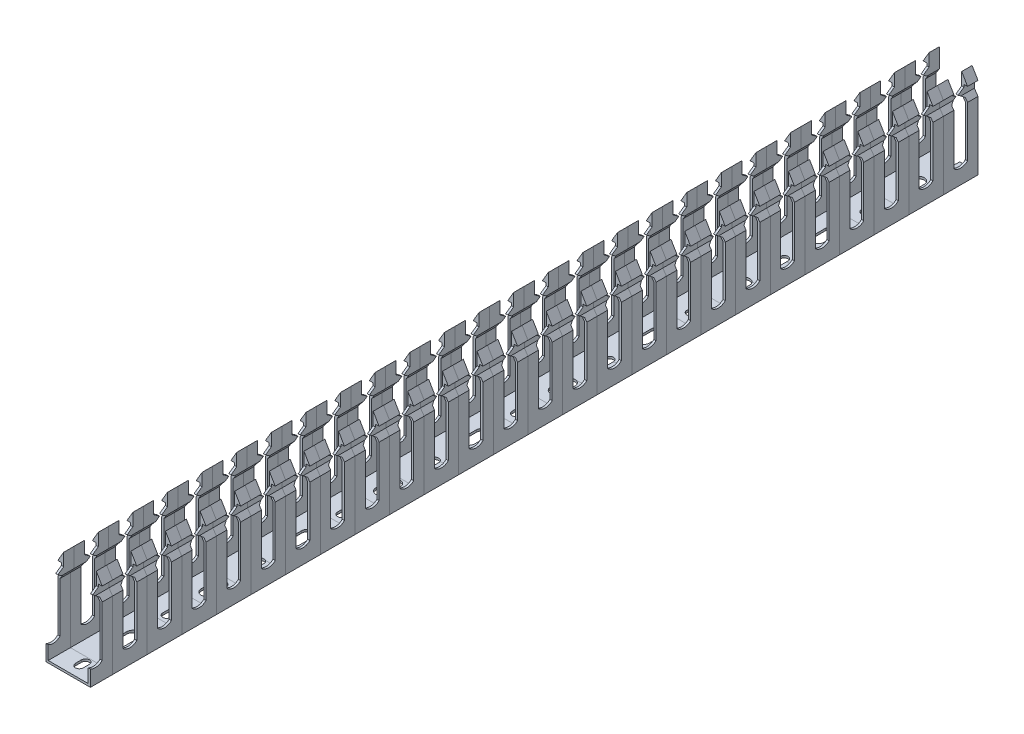
SolidWorks part; units mm, degrees
ref_plane "Front Plane" through (0, 0, 0) normal (0, 0, 1) x (1, 0, 0)
ref_plane "Top Plane" through (0, 0, 0) normal (0, 1, 0) x (1, 0, 0)
ref_plane "Right Plane" through (0, 0, 0) normal (1, 0, 0) x (0, 0, -1)
sketch "Sketch1" plane through (0, 0, 0) normal (0, 0, 1) x (1, 0, 0)
  line L1 (-12.7, -26.289) -> (12.7, -26.289)
  line L2 (-12.7, -26.289) -> (-12.7, 26.289)
  line L3 (-12.7, 26.289) -> (12.7, 26.289)
  line L4 (12.7, -26.289) -> (12.7, 26.289)
  line L5 (-12.7, -26.289) -> (12.7, 26.289) construction
  line L6 (-12.7, 26.289) -> (12.7, -26.289) construction
  point P0 (0, 0)
  dimension "D1" = 25.4
  dimension "D2" = 52.578
extrude "Boss-Extrude1" add sketch "Sketch1" along normal blind 19.812
sketch "Sketch2" plane through (12.7, 0, 0) normal (1, 0, 0) x (0, 0, -1)
  line L0 (-5.969, 26.289) -> (-5.969, 19.1453)
  line L1 (-19.812, 26.289) -> (0, 26.289) construction
  line L2 (-5.969, 19.1453) -> (-9.271, 16.764)
  line L3 (-9.271, 16.764) -> (-5.969, 14.3827)
  line L4 (-5.969, 14.3827) -> (-5.969, -16.3195)
  line L5 (-13.843, 26.289) -> (-13.843, 19.1453)
  line L6 (-13.843, 19.1453) -> (-10.541, 16.764)
  line L7 (-10.541, 16.764) -> (-13.843, 14.3827)
  line L8 (-13.843, 14.3827) -> (-13.843, -16.3195)
  line L9 (-13.843, 26.289) -> (-5.969, 26.289)
  line L10 (-13.843, -16.3195) -> (-5.969, -16.3195) construction
  line L11 (-10.541, 16.764) -> (-9.271, 16.764) construction
  line L12 (-13.843, 14.3827) -> (-5.969, 14.3827) construction
  line L13 (-13.843, 19.1453) -> (-5.969, 19.1453) construction
  line L14 (0, -26.289) -> (0, 26.289) construction
  line L15 (-13.843, 19.1453) -> (-13.843, 14.3827) construction
  line L16 (-5.969, 19.1453) -> (-5.969, 14.3827) construction
  line L17 (-19.812, -26.289) -> (0, -26.289) construction
  arc A0 (-5.969, -16.3195) -> (-13.843, -16.3195) centre (-9.906, -12.3825) cw
  dimension "D7" = 5.5678
  dimension "D1" = 7.874
  dimension "D2" = 1.27
  dimension "D3" = 9.525
  dimension "D4" = 7.1438
  dimension "D5" = 5.969
  dimension "D6" = 9.9695
extrude "Cut-Extrude2" cut sketch "Sketch2" against normal up to next
sketch "Sketch3" plane through (0, 0, 19.812) normal (0, 0, 1) x (1, 0, 0)
  line L0 (-11.43, 12.2331) -> (-11.43, -25.019)
  line L1 (-11.43, -25.019) -> (11.43, -25.019)
  line L2 (11.43, -25.019) -> (11.43, 12.2331)
  line L3 (11.43, 12.2331) -> (9.3339, 15.2441)
  line L4 (9.3339, 15.2441) -> (9.3339, 26.289)
  line L5 (12.7, 26.289) -> (-12.7, 26.289) construction
  line L6 (9.3339, 26.289) -> (12.7, 20.5631)
  line L7 (12.7, -26.289) -> (12.7, 26.289) construction
  line L8 (12.7, 20.5631) -> (10.6039, 20.5631)
  line L9 (10.6039, 20.5631) -> (10.6039, 15.6427)
  line L10 (-12.7, 26.289) -> (-12.7, -26.289) construction
  line L11 (10.6039, 15.6427) -> (13.6788, 11.2257)
  line L12 (-12.7, 20.5631) -> (-9.3339, 26.289)
  line L13 (-9.3339, 26.289) -> (-9.3339, 15.2441)
  line L14 (-9.3339, 15.2441) -> (-11.43, 12.2331)
  line L15 (-9.3339, 15.2441) -> (9.3339, 15.2441) construction
  line L16 (-12.7, 20.5631) -> (12.7, 20.5631) construction
  line L17 (13.6788, 11.2257) -> (13.6788, 29.8905)
  line L18 (13.6788, 29.8905) -> (-13.6788, 29.8905)
  line L19 (-13.6788, 29.8905) -> (-13.6788, 11.2257)
  line L20 (-13.6788, 11.2257) -> (-10.6039, 15.6427)
  line L21 (-10.6039, 15.6427) -> (-10.6039, 20.5631)
  line L22 (-10.6039, 20.5631) -> (-12.7, 20.5631)
  line L23 (-13.6788, 11.2257) -> (13.6788, 11.2257) construction
  line L24 (-12.7, -26.289) -> (12.7, -26.289) construction
  point P26 (0, 0)
  point P27 (0, 0)
  point P28 (-13.6788, 29.8905)
  point P29 (0, 0)
  point P30 (10.6676, 21.3409)
  point P31 (11.43, 12.9877)
  dimension "D1" = 1.27
  dimension "D2" = 1.27
  dimension "D3" = 1.27
  dimension "D4" = 1.27
  dimension "D5" = 1.27
  dimension "D6" = 27.3575
extrude "Cut-Extrude3" cut sketch "Sketch3" against normal up to surface (19.812 mm away) up to face at (0, 0, 0)
pattern_linear "LPattern1" count 26 spacing 19.812 along (0, 0, 1) of "Cut-Extrude3"
sketch "Sketch4" plane through (0, -26.289, 0) normal (0, -1, 0) x (1, 0, 0)
  line L0 (-12.7, 0) -> (12.7, 0) construction
  line L1 (-19.05, 508) -> (19.05, 508)
  line L2 (-19.05, 508) -> (-19.05, 520.7)
  line L3 (-19.05, 520.7) -> (19.05, 520.7)
  line L4 (19.05, 508) -> (19.05, 520.7)
  line L5 (-19.05, 508) -> (19.05, 520.7) construction
  line L6 (-19.05, 520.7) -> (19.05, 508) construction
  line L7 (12.7, 515.112) -> (12.7, 495.3) construction
  point P0 (0, 514.35)
  dimension "D1" = 508
  dimension "D2" = 12.7
  dimension "D3" = 38.1
  dimension "D4" = 6.35
extrude "Cut-Extrude4" cut sketch "Sketch4" against normal up to next
sketch "Sketch6" plane through (0, -26.289, 0) normal (0, -1, 0) x (1, 0, 0)
  line L0 (0, -1.7526) -> (0, 1.7526) construction
  line L1 (-2.2479, -1.7526) -> (-2.2479, 1.7526)
  line L2 (2.2479, -1.7526) -> (2.2479, 1.7526)
  line L3 (0, 21.2471) -> (0, 28.7401) construction
  line L4 (-3.2512, 21.2471) -> (-3.2512, 28.7401)
  line L5 (3.2512, 21.2471) -> (3.2512, 28.7401)
  line L6 (-12.7, 0) -> (12.7, 0) construction
  arc A0 (-2.2479, -1.7526) -> (2.2479, -1.7526) centre (0, -1.7526) ccw
  arc A1 (2.2479, 1.7526) -> (-2.2479, 1.7526) centre (0, 1.7526) ccw
  arc A2 (-3.2512, 21.2471) -> (3.2512, 21.2471) centre (0, 21.2471) ccw
  arc A3 (3.2512, 28.7401) -> (-3.2512, 28.7401) centre (0, 28.7401) ccw
  point P3 (0, 0)
  point P8 (0, 24.9936)
  dimension "D1" = 4.4958
  dimension "D2" = 8.001
  dimension "D3" = 6.5024
  dimension "D4" = 13.9954
  dimension "D5" = 0
  dimension "D6" = 24.9936
extrude "Cut-Extrude6" cut sketch "Sketch6" against normal up to surface (1.27 mm away) up to face at (0, -25.019, 9.906)
pattern_linear "LPattern2" count 11 spacing 49.9872 along (0, 0, 1) of "Cut-Extrude6"
equation "\"D4@Sketch2\"=\"D3@Sketch2\"*.75"
